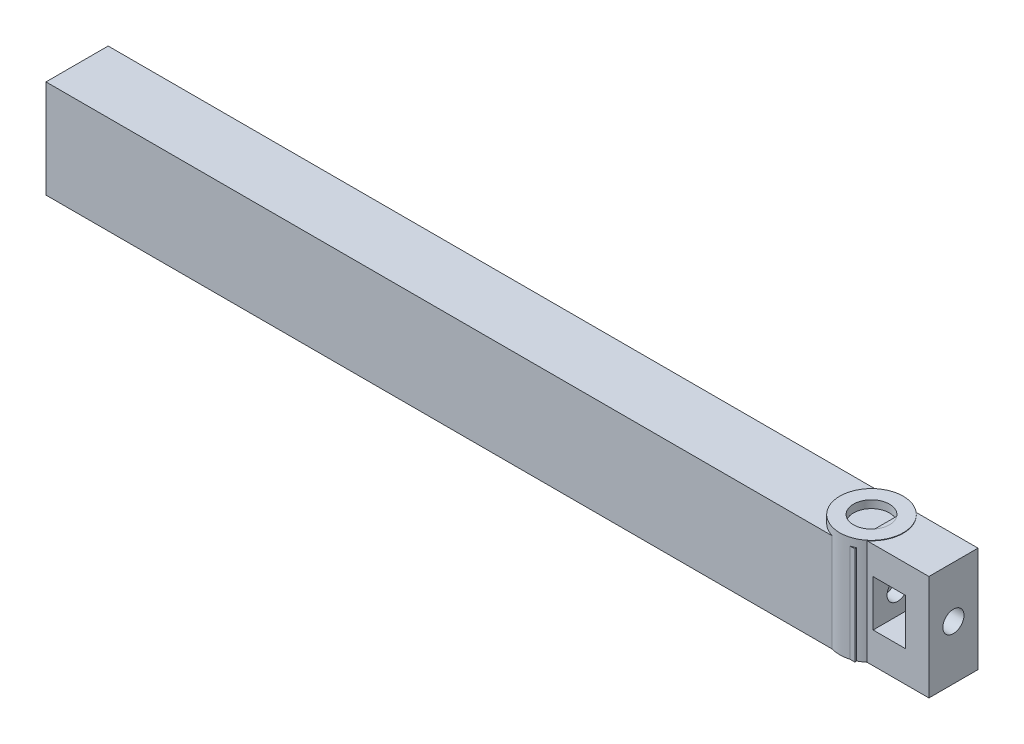
SolidWorks part; units mm, degrees
ref_plane "Front Plane" through (0, 0, 0) normal (0, 0, 1) x (1, 0, 0)
ref_plane "Top Plane" through (0, 0, 0) normal (0, 1, 0) x (1, 0, 0)
ref_plane "Right Plane" through (0, 0, 0) normal (1, 0, 0) x (0, 0, -1)
sketch "Sketch1" plane through (0, 0, 0) normal (0, 1, 0) x (1, 0, 0)
  circle A0 centre (0, 0) radius 6
extrude "Boss-Extrude1" add sketch "Sketch1" along normal blind 20
sketch "Sketch2" plane through (0, 20, 0) normal (0, 1, 0) x (1, 0, 0)
  circle A0 centre (0, 0) radius 3.4
extrude "Cut-Extrude1" cut sketch "Sketch2" against normal blind 13.55 contours A0
ref_plane "Plane1" through (0, 18.26, 0) normal (0, 1, 0) x (1, 0, 0)
ref_axis "Axis1" through (0, 6.45, 0) along (0, 1, 0)
ref_point "Point2"
sketch "Sketch5" plane through (0, 18.26, 0) normal (0, 1, 0) x (1, 0, 0)
  line L0 (0, 0) -> (2.6, 0) construction
  line L2 (2.6, -3.5716) -> (4.1507, -3.5716)
  line L3 (2.6, -3.5716) -> (2.6, 3.6126)
  line L4 (2.6, 3.6126) -> (4.1507, 3.6126)
  line L5 (4.1507, -3.5716) -> (4.1507, 3.6126)
extrude "Boss-Extrude2" add sketch "Sketch5" against normal blind 13.55
sketch "Sketch7" plane through (2.6, 0, 0) normal (-1, 0, 0) x (0, 0, 1)
  line L1 (-4.6485, 19.91) -> (4.638, 19.91)
  line L2 (-4.6485, 19.91) -> (-4.6485, 0)
  line L3 (-4.6485, 0) -> (4.638, 0)
  line L4 (4.638, 19.91) -> (4.638, 0)
extrude "Boss-Extrude3" add sketch "Sketch7" against normal blind 12.9
sketch "Sketch6" plane through (2.6, 0, 0) normal (-1, 0, 0) x (0, 0, 1)
  line L1 (-2.1909, 6.45) -> (-2.1909, 19.91) construction
  line L2 (2.1909, 19.91) -> (2.1909, 6.45) construction
  line L3 (-2.1909, 15.4522) -> (2.1909, 15.4522) construction
  circle A0 centre (0, 10.2369) radius 2
  point P0 (0, 10.2369)
  point P12 (0, 0)
extrude "Cut-Extrude2" cut sketch "Sketch6" against normal blind 13.55 and the other way blind 1
ref_axis "Axis2" through (-1.8994, 10.2369, 0) along (-1, 0, 0)
ref_axis "Axis4" through (15.5, 10.2369, 0) along (-1, 0, 0)
ref_plane "Plane3" through (0, 0, 0) normal (0, 0, 1) x (1, 0, 0)
sketch "Sketch9" plane through (0, 0, 0) normal (0, 0, 1) x (1, 0, 0)
  line L0 (11.0634, 10.2369) -> (11.0634, 5.8619)
  line L1 (4.9434, 5.8619) -> (11.0634, 5.8619)
  line L2 (4.9434, 5.8619) -> (4.9434, 10.2369)
  line L3 (4.9434, 10.2369) -> (4.9434, 14.6119)
  line L4 (4.9434, 14.6119) -> (11.0634, 14.6119)
  line L5 (11.0634, 14.6119) -> (11.0634, 10.2369)
  line L6 (15.5, 10.2369) -> (2.6, 10.2369) construction
  point P5 (10.3875, 10.2369)
  point P9 (4.9434, 10.2369)
extrude "Cut-Extrude3" cut sketch "Sketch9" against normal blind 10 and the other way blind 10
sketch "Sketch11" plane through (2.6, 0, 0) normal (-1, 0, 0) x (0, 0, 1)
  line L1 (-5.9922, 18.5514) -> (5.764, 18.5514)
  line L2 (-5.9922, 18.5514) -> (-5.9922, 0)
  line L3 (-5.9922, 0) -> (5.764, 0)
  line L4 (5.764, 18.5514) -> (5.764, 0)
extrude "Boss-Extrude4" add sketch "Sketch11" along normal blind 153
